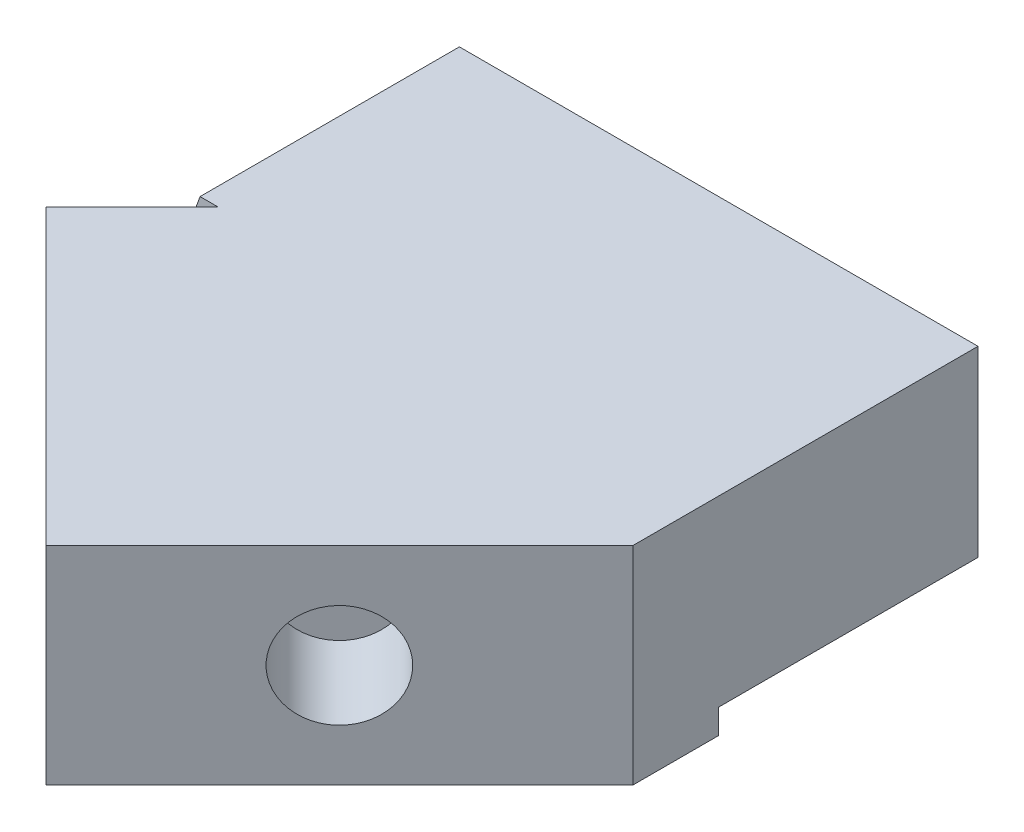
SolidWorks part; units mm, degrees
ref_plane "Front Plane" through (0, 0, 0) normal (0, 0, 1) x (1, 0, 0)
ref_plane "Top Plane" through (0, 0, 0) normal (0, 1, 0) x (1, 0, 0)
ref_plane "Right Plane" through (0, 0, 0) normal (1, 0, 0) x (0, 0, -1)
sketch "Sketch1" plane through (0, 0, 0) normal (0, 1, 0) x (1, 0, 0)
  line L0 (-35.921, 0) -> (0, 35.921)
  line L1 (-35.921, 0) -> (0, -35.921)
  line L2 (0, 35.921) -> (35.921, 0)
  line L3 (0, -35.921) -> (35.921, 0)
  line L4 (-35.921, 0) -> (35.921, 0) construction
  line L5 (0, 35.921) -> (0, -35.921) construction
  point P1 (0, 0)
  dimension "D1" = 50.8
  dimension "D2" = 50.8
extrude "Boss-Extrude1" add sketch "Sketch1" along normal mid plane 25.4
sketch "Sketch2" plane through (17.9605, 0, 17.9605) normal (0.7071, 0, 0.7071) x (0.7071, 0, -0.7071)
  circle A0 centre (0, 0) radius 6.35
  dimension "D1" = 12.7
extrude "Cut-Extrude1" cut sketch "Sketch2" against normal blind 12.7
sketch "Sketch3" plane through (-17.9605, 0, 17.9605) normal (-0.7071, 0, 0.7071) x (0.7071, 0, 0.7071)
  circle A0 centre (0, 0) radius 6.35
  dimension "D1" = 12.7
extrude "Cut-Extrude2" cut sketch "Sketch3" against normal blind 12.7
sketch "Sketch4" plane through (0, 12.7, 0) normal (0, 1, 0) x (1, 0, 0)
  line L0 (25.4, 10.521) -> (-25.4, 10.521)
  line L1 (35.921, 0) -> (0, 35.921) construction
  line L2 (0, 35.921) -> (-35.921, 0) construction
  line L3 (-25.4, 10.521) -> (0, 35.921)
  line L4 (0, 35.921) -> (25.4, 10.521)
  dimension "D1" = 25.4
extrude "Cut-Extrude3" cut sketch "Sketch4" against normal through all
sketch "Sketch5" plane through (0, 0, -10.521) normal (0, 0, -1) x (-1, 0, 0)
  line L0 (-35.921, 12.7) -> (-35.921, -12.7)
  line L1 (-35.921, -12.7) -> (36.8238, -12.7)
  line L2 (36.8238, -12.7) -> (27.579, 12.7)
  line L3 (27.579, 12.7) -> (-35.921, 12.7)
  line L4 (25.4, -12.7) -> (-25.4, -12.7) construction
  line L5 (-35.921, 12.7) -> (-35.921, -12.7) construction
  line L8 (25.4, 12.7) -> (-25.4, 12.7) construction
  point P6 (0, 0)
  dimension "D1" = 70
  dimension "D2" = 63.5
extrude "Boss-Extrude2" add sketch "Sketch5" against normal up to surface and the other way blind 31.75 up to face at (30.6605, 0, -5.2605)
sketch "Sketch6" plane through (-28.4345, 10.3493, 0) normal (-0.9397, 0.342, 0) x (0, 0, 1)
  line L0 (-42.271, -24.5286) -> (-42.271, 2.5015) construction
  line L1 (-42.271, -24.5286) -> (-10.521, -24.5286) construction
  circle A0 centre (-26.396, -11.0135) radius 6.35
  point P4 (-42.271, -11.0135)
  point P7 (-26.396, -24.5286)
  dimension "D1" = 12.7
extrude "Cut-Extrude4" cut sketch "Sketch6" against normal through all
sketch "Sketch7" plane through (0, 0, -42.271) normal (0, 0, -1) x (-1, 0, 0)
  line L0 (-44.1983, -12.7) -> (21.379, 11.1682)
  line L1 (-35.921, -12.7) -> (36.8238, -12.7) construction
  line L3 (21.379, 11.1682) -> (30.0663, -12.7)
  line L4 (-44.1983, -12.7) -> (30.0663, -12.7)
  line L5 (36.8238, -12.7) -> (27.579, 12.7) construction
  dimension "D1" = 25.4
  dimension "D3" = 6.35
extrude "Cut-Extrude5" cut sketch "Sketch7" against normal blind 31.75
sketch "Sketch8" plane through (0, 12.7, 0) normal (0, 1, 0) x (1, 0, 0)
  line L5 (-42.1413, -6.2203) -> (-8.2965, -39.8855)
  line L6 (0, -35.921) -> (0, -57.0039)
  line L13 (0, -57.0039) -> (-46.5861, -10.6651)
  line L14 (-46.5861, -10.6651) -> (-42.1413, -6.2203)
  line L15 (-8.2965, -39.8855) -> (-8.2965, -27.6245)
  line L16 (-35.921, 0) -> (0, -35.921) construction
  line L17 (-8.2965, -27.6245) -> (0, -35.921)
  line L18 (-25.4, 10.521) -> (-35.921, 0) construction
extrude "Boss-Extrude3" [suppressed] add sketch "Sketch8" against normal up to surface (25.4 mm away) up to face at (2.1042, -12.7, 2.9758)
